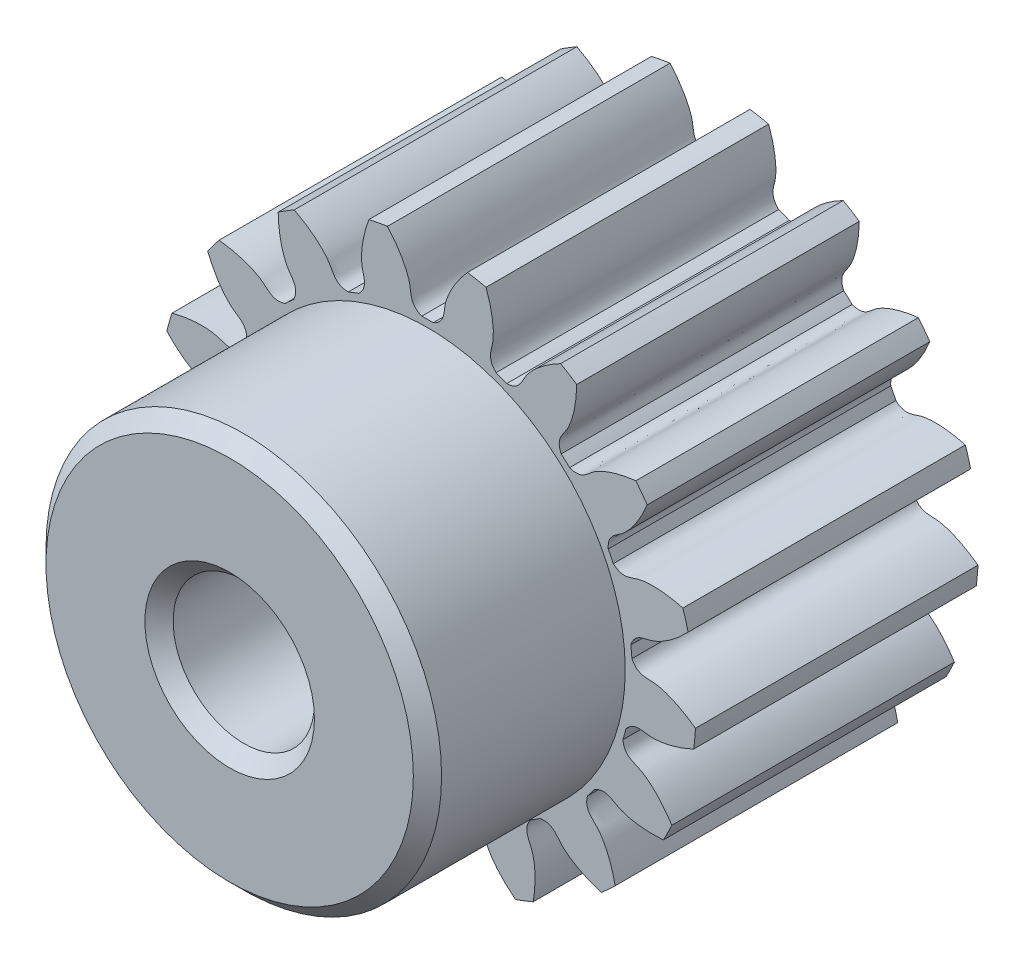
SolidWorks part; units mm, degrees
ref_plane "前视基准面" through (0, 0, 0) normal (0, 0, 1) x (1, 0, 0)
ref_plane "上视基准面" through (0, 0, 0) normal (0, 1, 0) x (1, 0, 0)
ref_plane "右视基准面" through (0, 0, 0) normal (1, 0, 0) x (0, 0, -1)
sketch "草图1" plane through (0, 0, 0) normal (0, 0, 1) x (1, 0, 0)
  circle A0 centre (0, 0) radius 19
extrude "凸台-拉伸1" add sketch "草图1" along normal blind 20
ref_axis "基准轴1" through (0, 0, 20) along (0, 0, -1)
sketch "草图2" plane through (0, 0, 0) normal (0, 0, 1) x (1, 0, 0)
  line L0 (0, 0) -> (0, 19) construction
  circle A0 centre (0, 0) radius 19 construction
  arc A1 (0.4034, 14.4944) -> (-0.4034, 14.4944) centre (0, 0) ccw
  arc A2 (6.2313, 21.4814) -> (-6.2313, 21.4814) centre (0, 0) ccw
  spline S0 degree 3 poles (0.4034, 14.4944) (1.2558, 14.8496) (1.1324, 15.5096) (1.2766, 16.1296) (1.29, 16.1823) (1.306, 16.2408) (1.3251, 16.3052) (1.3474, 16.3752) (1.3731, 16.4508) (1.4025, 16.5319) (1.4359, 16.6184) (1.4733, 16.7101) (1.5152, 16.8068) (1.5616, 16.9086) (1.6128, 17.0151) (1.669, 17.1264) (1.7304, 17.2421) (1.7972, 17.3621) (1.8696, 17.4863) (1.9478, 17.6145) (2.032, 17.7465) (2.1224, 17.8821) (2.2191, 18.0211) (2.3223, 18.1634) (2.4322, 18.3086) (2.5489, 18.4566) (2.6727, 18.6072) (2.8035, 18.7601) (2.9417, 18.9152) (3.0873, 19.0722) (3.2404, 19.2308) (3.4012, 19.3908) (3.5698, 19.552) (3.7462, 19.7141) (3.9307, 19.8769) (4.1233, 20.0401) (4.324, 20.2035) (4.533, 20.3667) (4.7503, 20.5295) (4.9761, 20.6917) (5.2103, 20.853) (5.453, 21.0131) (5.7916, 21.2269) (6.0532, 21.3811) (6.2313, 21.4814) knots 0 0 0 0 0.193883 0.199024 0.204851 0.211363 0.21856 0.226443 0.235011 0.244265 0.254205 0.264829 0.27614 0.288136 0.300817 0.314184 0.328236 0.342973 0.358397 0.374505 0.391299 0.408779 0.426944 0.445795 0.465331 0.485552 0.506459 0.528051 0.550329 0.573293 0.596941 0.621276 0.646296 0.672001 0.698392 0.725468 0.753229 0.781677 0.810809 0.840627 0.871131 0.90232 0.934195 1 1 1 1
  spline S1 degree 3 poles (-0.4034, 14.4944) (-1.2558, 14.8496) (-1.1324, 15.5096) (-1.2766, 16.1296) (-1.29, 16.1823) (-1.306, 16.2408) (-1.3251, 16.3052) (-1.3474, 16.3752) (-1.3731, 16.4508) (-1.4025, 16.5319) (-1.4359, 16.6184) (-1.4733, 16.7101) (-1.5152, 16.8068) (-1.5616, 16.9086) (-1.6128, 17.0151) (-1.669, 17.1264) (-1.7304, 17.2421) (-1.7972, 17.3621) (-1.8696, 17.4863) (-1.9478, 17.6145) (-2.032, 17.7465) (-2.1224, 17.8821) (-2.2191, 18.0211) (-2.3223, 18.1634) (-2.4322, 18.3086) (-2.5489, 18.4566) (-2.6727, 18.6072) (-2.8035, 18.7601) (-2.9417, 18.9152) (-3.0873, 19.0722) (-3.2404, 19.2308) (-3.4012, 19.3908) (-3.5698, 19.552) (-3.7462, 19.7141) (-3.9307, 19.8769) (-4.1233, 20.0401) (-4.324, 20.2035) (-4.533, 20.3667) (-4.7503, 20.5295) (-4.9761, 20.6917) (-5.2103, 20.853) (-5.453, 21.0131) (-5.7916, 21.2269) (-6.0532, 21.3811) (-6.2313, 21.4814) knots 0 0 0 0 0.193883 0.199024 0.204851 0.211363 0.21856 0.226443 0.235011 0.244265 0.254205 0.264829 0.27614 0.288136 0.300817 0.314184 0.328236 0.342973 0.358397 0.374505 0.391299 0.408779 0.426944 0.445795 0.465331 0.485552 0.506459 0.528051 0.550329 0.573293 0.596941 0.621276 0.646296 0.672001 0.698392 0.725468 0.753229 0.781677 0.810809 0.840627 0.871131 0.90232 0.934195 1 1 1 1
extrude "切除-拉伸1" cut sketch "草图2" along normal through all
pattern_circular "阵列(圆周)1" count 17 every 21.176 about axis through (0, 0, 20) along (0, 0, -1) of "切除-拉伸1"
sketch "草图3" plane through (0, 0, 0) normal (0, 0, 1) x (1, 0, 0)
  circle A0 centre (0, 0) radius 17 construction
  dimension "Dn" = 34
sketch "草图4" plane through (0, 0, 20) normal (0, 0, 1) x (1, 0, 0)
  circle A0 centre (0, 0) radius 14
  dimension "D1" = 28
extrude "凸台-拉伸2" add sketch "草图4" along normal blind 14
sketch "草图5" plane through (0, 0, 34) normal (0, 0, 1) x (1, 0, 0)
  circle A0 centre (0, 0) radius 5
  dimension "D1" = 10
extrude "切除-拉伸2" cut sketch "草图5" against normal through all
chamfer "倒角1" distance 1 angle 45 3 edges at (5, 0, 0) (5, 0, 34) (14, 0, 34)
